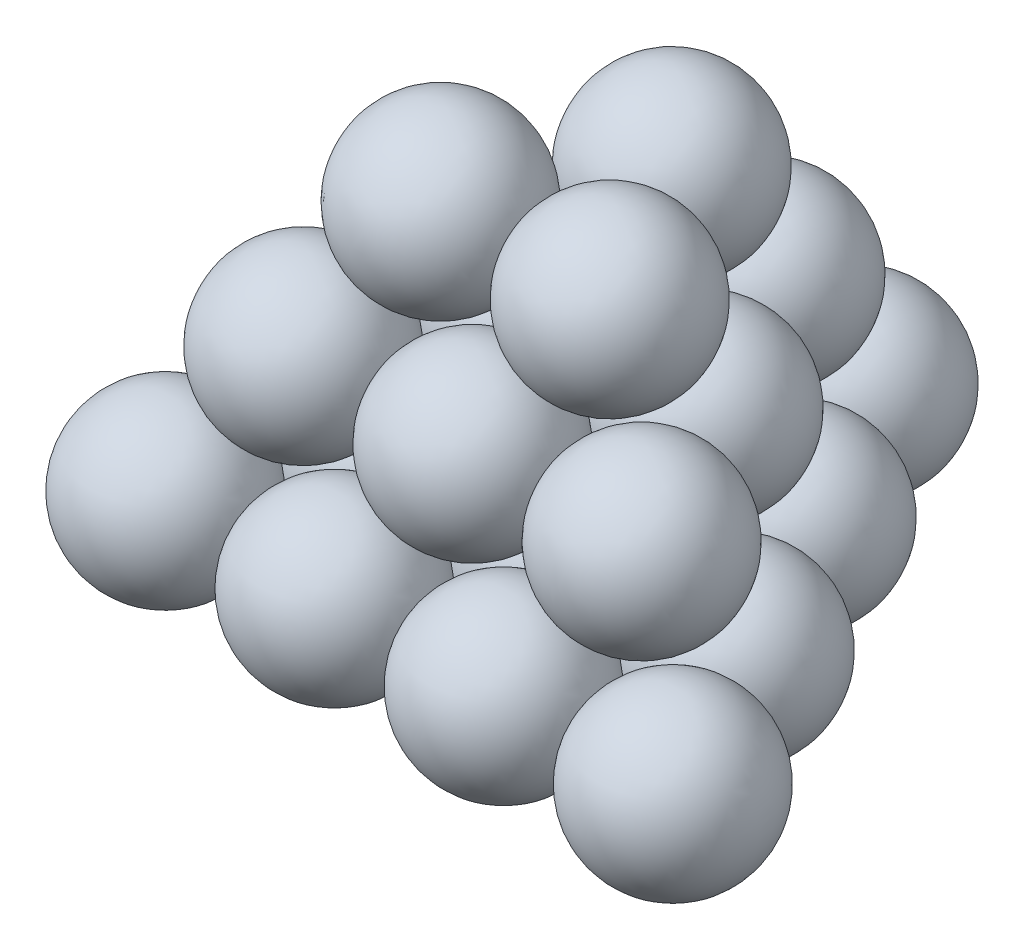
SolidWorks part; units mm, degrees
ref_plane "前基準面" through (0, 0, 0) normal (0, 0, 1) x (1, 0, 0)
ref_plane "上基準面" through (0, 0, 0) normal (0, 1, 0) x (1, 0, 0)
ref_plane "右基準面" through (0, 0, 0) normal (1, 0, 0) x (0, 0, -1)
sketch "草圖1" plane through (0, 0, 0) normal (0, 0, 1) x (1, 0, 0)
  line L0 (0, 30) -> (0, -57.2417)
  line L1 (0, 30) -> (0, -30)
  line L2 (60, 30) -> (60, -30)
  line L3 (120, 30) -> (120, -30)
  line L4 (60, 30) -> (60, -63.2368)
  line L5 (180, 0) -> (228.3593, 0)
  line L6 (60, -63.2368) -> (60, -30)
  line L7 (120, -30) -> (120, -48.9727)
  line L8 (120, -48.9727) -> (120, -30)
  line L9 (180, 30) -> (180, -58.9066) construction
  line L10 (120.355, 18.9908) -> (120.355, -41.0092)
  line L11 (180, 30) -> (180, -30)
  arc A0 (0, -30) -> (0, 30) centre (0, 0) ccw
  arc A1 (60, -30) -> (60, 30) centre (60, 0) ccw
  arc A2 (120, -30) -> (120, 30) centre (120, 0) ccw
  arc A3 (180, -30) -> (180, 30) centre (180, 0) ccw
  dimension "D1" = 60
  dimension "D2" = 60
  dimension "D3" = 60
  dimension "D4" = 60
  dimension "D5" = 60
  dimension "D6" = 60
revolve "旋轉1" add sketch "草圖1" angle 360 about L0 region at (12.7324, 0, 0)
revolve "旋轉2" add sketch "草圖1<8>" angle 360 about L4 region at (72.7324, 0, 0)
sketch "草圖1<8>" plane through (0, 0, 0) normal (0, 0, 1) x (1, 0, 0) same geometry as "草圖1"
revolve "旋轉3" add sketch "草圖1<9>" angle 360 about L7 region at (132.7324, 0, 0)
sketch "草圖1<9>" plane through (0, 0, 0) normal (0, 0, 1) x (1, 0, 0) same geometry as "草圖1"
revolve "旋轉4" add sketch "草圖1<10>" angle 360 about L9 region at (192.7324, 12.7324, 0) region at (192.7324, -12.7324, 0)
sketch "草圖1<10>" plane through (0, 0, 0) normal (0, 0, 1) x (1, 0, 0) same geometry as "草圖1"
sketch "草圖2" plane through (0, 0, 0) normal (0, 1, 0) x (1, 0, 0)
  line L0 (0, 0) -> (30, 51.9615) construction
  line L1 (0, 0) -> (291.9104, 0) construction
  line L2 (180, 0) -> (150, 51.9615) construction
  line L3 (90, 125.8846) -> (90, -89.0854) construction
  line L4 (-15.5515, 51.9615) -> (219.1598, 51.9615) construction
  line L5 (12.7587, 103.923) -> (215.2095, 103.923) construction
  line L6 (42.0565, 155.8846) -> (157.9307, 155.8846) construction
  line L7 (90, 155.8846) -> (77.84, 176.9464) construction
  line L8 (90, 155.8846) -> (122.0023, 211.3142) construction
  line L9 (60, 103.923) -> (75, 129.9038) construction
  line L10 (120, 103.923) -> (105, 129.9038) construction
  line L11 (60, 155.8846) -> (120, 155.8846)
  line L12 (30, 103.923) -> (90, 103.923)
  line L13 (150, 103.923) -> (90, 103.923)
  line L14 (0, 51.9615) -> (60, 51.9615)
  line L15 (120, 51.9615) -> (180, 51.9615)
  arc A0 (0, 51.9615) -> (60, 51.9615) centre (30, 51.9615) ccw
  arc A1 (90, 103.923) -> (30, 103.923) centre (60, 103.923) ccw
  arc A2 (120, 155.8846) -> (60, 155.8846) centre (90, 155.8846) ccw
  circle A3 centre (0, 0) radius 30 construction
  arc A4 (180, 51.9615) -> (120, 51.9615) centre (150, 51.9615) cw
  arc A5 (90, 103.923) -> (150, 103.923) centre (120, 103.923) cw
  dimension "D3" = 60
  dimension "D4" = 60
  dimension "D5" = 60
  dimension "D2" = 60
revolve "旋轉5" add sketch "草圖2" angle 360 about L5 region at (60, 0, -116.6554) region at (120, 0, -116.6554)
revolve "旋轉6" add sketch "草圖2<5>" angle 360 about L4 region at (30, 0, -39.2291) region at (150, 0, -39.2291)
sketch "草圖2<5>" plane through (0, 0, 0) normal (0, 1, 0) x (1, 0, 0) same geometry as "草圖2"
revolve "旋轉7" add sketch "草圖2<6>" angle 360 about L6 region at (90, 0, -168.617)
sketch "草圖2<6>" plane through (0, 0, 0) normal (0, 1, 0) x (1, 0, 0) same geometry as "草圖2"
sketch "草圖3" plane through (0, 0, 0) normal (0, 1, 0) x (1, 0, 0)
  line L0 (120, 51.9615) -> (120, 102.0057)
  line L1 (60, 51.9615) -> (120, 51.9615)
  line L2 (47.9496, 51.9615) -> (223.7479, 51.9615) construction
  circle A2 centre (150, 51.9615) radius 30 construction
  circle A3 centre (150, 51.9615) radius 30
  arc A4 (60, 51.9615) -> (120, 51.9615) centre (90, 51.9615) cw
revolve "旋轉8" add sketch "草圖3" angle 360 about L2 region at (90, 0, -64.6939)
ref_plane "平面1" through (0, 50, 0) normal (0, 1, 0) x (1, 0, 0)
sketch "草圖4" plane through (0, 50, 0) normal (0, 1, 0) x (1, 0, 0)
  line L0 (30, 18.938) -> (263.9911, 18.938) construction
  line L1 (30, 18.938) -> (133.624, 198.42) construction
  line L2 (150, 18.938) -> (50.8505, 190.6701) construction
  line L3 (90, 155.8846) -> (90, 203.5479) construction
  line L4 (60, 155.8846) -> (60, 190.6701)
  line L5 (60, 122.8611) -> (120, 122.8611)
  line L6 (120, 122.8611) -> (179.1424, 122.8611) construction
  line L7 (150, 70.8996) -> (30, 70.8996)
  line L8 (30, 70.8996) -> (-19.1209, 70.8996) construction
  line L9 (0, 18.938) -> (180, 18.938)
  line L10 (180, 18.938) -> (232.962, 18.938) construction
  arc A0 (0, 18.938) -> (60, 18.938) centre (30, 18.938) ccw
  arc A2 (120, 18.938) -> (180, 18.938) centre (150, 18.938) ccw
  arc A3 (30, 70.8996) -> (90, 70.8996) centre (60, 70.8996) ccw
  circle A4 centre (90, 155.8846) radius 30 construction
  arc A6 (150, 70.8996) -> (90, 70.8996) centre (120, 70.8996) cw
  arc A7 (120, 122.8611) -> (60, 122.8611) centre (90, 122.8611) ccw
  arc A8 (60, 18.938) -> (120, 18.938) centre (90, 18.938) ccw
  dimension "D3" = 60
  dimension "D4" = 60
  dimension "D5" = 60
  dimension "D1" = 60
  dimension "D2" = 60
  dimension "D7" = 60
  dimension "D8" = 47.6633
  dimension "D9" = 34.7855
  dimension "D10" = 30
  dimension "D12" = 60
revolve "旋轉9" add sketch "草圖4" angle 360 about L6 region at (90, 50, -135.5935)
revolve "旋轉10" add sketch "草圖4<6>" angle 360 about L8 region at (120, 50, -58.1672) region at (60, 50, -58.1672)
sketch "草圖4<6>" plane through (0, 50, 0) normal (0, 1, 0) x (1, 0, 0) same geometry as "草圖4"
revolve "旋轉11" add sketch "草圖4<7>" angle 360 about L0 region at (150, 50, -6.2056) region at (90, 50, -6.2056) region at (30, 50, -6.2056)
sketch "草圖4<7>" plane through (0, 50, 0) normal (0, 1, 0) x (1, 0, 0) same geometry as "草圖4"
ref_plane "平面2" through (0, 100, 0) normal (0, 1, 0) x (1, 0, 0)
sketch "草圖5" plane through (0, 100, 0) normal (0, 1, 0) x (1, 0, 0)
  line L0 (60, 37.6297) -> (142.2168, 180.0333) construction
  line L1 (120, 37.6297) -> (42.162, 172.449) construction
  line L2 (60, 37.6297) -> (120, 37.6297) construction
  line L3 (90, 89.5912) -> (90, 192.4055)
  line L4 (60, 155.8846) -> (60, 190.1263)
  line L6 (60, 89.5912) -> (120, 89.5912)
  line L7 (120, 89.5912) -> (164.9045, 89.5912) construction
  line L8 (150, 37.6297) -> (193.9351, 37.6297) construction
  line L9 (30, 37.6297) -> (90, 37.6297)
  line L10 (150, 37.6297) -> (90, 37.6297)
  arc A0 (120, 89.5912) -> (60, 89.5912) centre (90, 89.5912) ccw
  arc A1 (30, 37.6297) -> (90, 37.6297) centre (60, 37.6297) ccw
  arc A2 (90, 37.6297) -> (150, 37.6297) centre (120, 37.6297) ccw
  circle A3 centre (90, 155.8846) radius 30 construction
  dimension "D1" = 60
  dimension "D3" = 60
  dimension "D7" = 60
  dimension "D4" = 60
  dimension "D5" = 60
  dimension "D6" = 30
  dimension "D8" = 60
revolve "旋轉12" add sketch "草圖5" angle 360 about L8 region at (120, 100, -24.8973) region at (60, 100, -24.8973)
revolve "旋轉13" add sketch "草圖5<5>" angle 360 about L7 region at (77.2676, 100, -102.3236) region at (102.7324, 100, -102.3236)
sketch "草圖5<5>" plane through (0, 100, 0) normal (0, 1, 0) x (1, 0, 0) same geometry as "草圖5"
ref_plane "平面3" through (0, 150, 0) normal (0, 1, 0) x (1, 0, 0)
